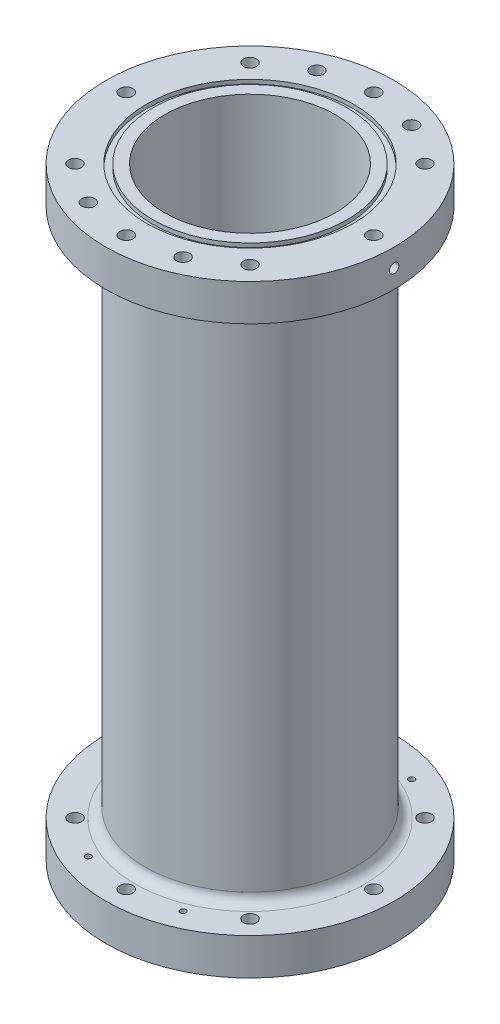
SolidWorks part; units mm, degrees
ref_plane "Front Plane" through (0, 0, 0) normal (0, 0, 1) x (1, 0, 0)
ref_plane "Top Plane" through (0, 0, 0) normal (0, 1, 0) x (1, 0, 0)
ref_plane "Right Plane" through (0, 0, 0) normal (1, 0, 0) x (0, 0, -1)
sketch "Sketch2" plane through (0, 0, 0) normal (0, 1, 0) x (1, 0, 0)
  circle A0 centre (0, 0) radius 41.275
  circle A1 centre (0, 0) radius 50.8
  dimension "D1" = 101.6
  dimension "D2" = 82.55
extrude "Base Cylinder" add sketch "Sketch2" along normal blind 292.1
sketch "Sketch3" plane through (0, 0, 0) normal (0, -1, 0) x (1, 0, 0)
  circle A0 centre (0, 0) radius 41.275
  circle A1 centre (0, 0) radius 69.85
  dimension "D1" = 139.7
extrude "Aft Flange" add sketch "Sketch3" against normal blind 17.78
sketch "Sketch4" plane through (0, 292.1, 0) normal (0, 1, 0) x (1, 0, 0)
  circle A0 centre (0, 0) radius 41.275
  circle A1 centre (0, 0) radius 69.85
extrude "Forward Flange" add sketch "Sketch4" against normal blind 17.78
sketch "Sketch6" plane through (0, 0, 0) normal (0, -1, 0) x (1, 0, 0)
  circle A0 centre (0, 0) radius 50.0761
  circle A1 centre (0, 0) radius 47.0027
  dimension "D1" = 100.1522
  dimension "D2" = 94.0054
extrude "O-Ring Slot 1" cut sketch "Sketch6" against normal blind 1.9812
sketch "Sketch7" plane through (0, 292.1, 0) normal (0, 1, 0) x (1, 0, 0)
  circle A0 centre (0, 0) radius 50.0761
  circle A1 centre (0, 0) radius 47.0027
  dimension "D1" = 100.1522
  dimension "D2" = 94.0054
extrude "O-Ring Slot 2" cut sketch "Sketch7" against normal blind 1.9812
sketch "Sketch8" plane through (0, 0, 0) normal (0, -1, 0) x (1, 0, 0)
  circle A0 centre (-59.9186, 0) radius 3.175
  circle A1 centre (-42.3688, 42.3688) radius 3.175
  circle A2 centre (0, 59.9186) radius 3.175
  circle A3 centre (42.3688, 42.3688) radius 3.175
  circle A4 centre (59.9186, 0) radius 3.175
  circle A5 centre (42.3688, -42.3688) radius 3.175
  circle A6 centre (0, -59.9186) radius 3.175
  circle A7 centre (-42.3688, -42.3688) radius 3.175
  point P36 (0, 0)
  dimension "D2" = 6.35
  dimension "D1" = 59.9186
  dimension "D3" = 8
extrude "Cut-Extrude4" cut sketch "Sketch8" against normal through all both and the other way through all
fillet "Fillet1" radius 4.7625 2 edges at (0, 17.78, -50.8) (0, 274.32, 50.8)
sketch "Sketch9" plane through (0, 292.1, 0) normal (0, 1, 0) x (1, 0, 0)
  line L0 (0, -76.2) -> (0, 76.2) construction
  line L1 (-32.6024, 78.7092) -> (32.6024, -78.7092) construction
  line L2 (-32.0538, -77.3847) -> (32.0538, 77.3847) construction
  circle A0 centre (0, 0) radius 59.9186 construction
  circle A1 centre (-22.9299, 55.3576) radius 3.175
  circle A2 centre (22.9299, -55.3576) radius 3.175
  circle A3 centre (22.9299, 55.3576) radius 3.175
  circle A4 centre (-22.9299, -55.3576) radius 3.175
  point P6 (0, 0)
  point P9 (0, 0)
  point P16 (0, 0)
  dimension "D1" = 119.8372
  dimension "D3" = 6.35
  dimension "D4" = 6.35
  dimension "D5" = 6.35
  dimension "D6" = 6.35
  dimension "D2" = 22.5
  dimension "D7" = 22.5
extrude "Cut-Extrude5" cut sketch "Sketch9" against normal blind 7.62
sketch "Sketch10" plane through (0, 0, 0) normal (0, -1, 0) x (1, 0, 0)
  line L0 (0, -76.2) -> (0, 76.2) construction
  line L1 (-33.7592, 81.5019) -> (33.7592, -81.5019) construction
  line L2 (-33.8465, -81.7128) -> (33.8465, 81.7128) construction
  circle A0 centre (0, 0) radius 59.9186 construction
  circle A1 centre (-22.9299, 55.3576) radius 3.175
  circle A2 centre (22.9299, -55.3576) radius 3.175
  circle A3 centre (22.9299, 55.3576) radius 3.175
  circle A4 centre (-22.9299, -55.3576) radius 3.175
  point P6 (0, 0)
  point P9 (0, 0)
  point P16 (0, 0)
  dimension "D1" = 119.8372
  dimension "D2" = 6.35
  dimension "D3" = 6.35
  dimension "D5" = 6.35
  dimension "D6" = 6.35
  dimension "D4" = 22.5
  dimension "D7" = 22.5
extrude "Cut-Extrude6" cut sketch "Sketch10" against normal blind 7.62
sketch "Sketch11" plane through (0, 284.48, 0) normal (0, 1, 0) x (1, 0, 0)
  circle A0 centre (-22.9299, 55.3576) radius 1.4097
  circle A1 centre (22.9299, 55.3576) radius 1.4097
  circle A2 centre (-22.9299, -55.3576) radius 1.4097
  circle A3 centre (22.9299, -55.3576) radius 1.4097
  dimension "D1" = 2.8194
  dimension "D2" = 2.8194
  dimension "D3" = 2.8194
  dimension "D4" = 2.8194
extrude "Cut-Extrude7" cut sketch "Sketch11" against normal up to next
sketch "Sketch12" plane through (0, 7.62, 0) normal (0, -1, 0) x (1, 0, 0)
  circle A0 centre (-22.9299, 55.3576) radius 1.4097
  circle A1 centre (22.9299, 55.3576) radius 1.4097
  circle A2 centre (-22.9299, -55.3576) radius 1.4097
  circle A3 centre (22.9299, -55.3576) radius 1.4097
  dimension "D1" = 2.8194
  dimension "D2" = 2.8194
  dimension "D3" = 2.8194
  dimension "D4" = 2.8194
extrude "Cut-Extrude8" cut sketch "Sketch12" against normal up to next
ref_plane "Plane1" through (-69.85, 0, 0) normal (1, 0, 0) x (0, 0, -1)
ref_plane "Plane3" through (69.85, 0, 0) normal (1, 0, 0) x (0, 0, -1)
ref_plane "Plane4" through (0, 283.21, 0) normal (0, 1, 0) x (1, 0, 0)
sketch "Sketch13" plane through (-69.85, 0, 0) normal (1, 0, 0) x (0, 0, -1)
  line L0 (76.835, 283.21) -> (-76.835, 283.21) construction
  circle A0 centre (0, 283.21) radius 2.3114
  dimension "D1" = 4.6228
extrude "Cut-Extrude10" cut sketch "Sketch13" along normal blind 6.35
sketch "Sketch14" plane through (69.85, 0, 0) normal (1, 0, 0) x (0, 0, -1)
  circle A0 centre (0, 283.21) radius 2.3114
  dimension "D1" = 4.6228
extrude "Cut-Extrude11" cut sketch "Sketch14" against normal blind 6.35
ref_axis "Axis1" through (63.5, 283.21, 0) along (1, 0, 0)
ref_axis "Axis2" through (-63.5, 283.21, 0) along (-1, 0, 0)
